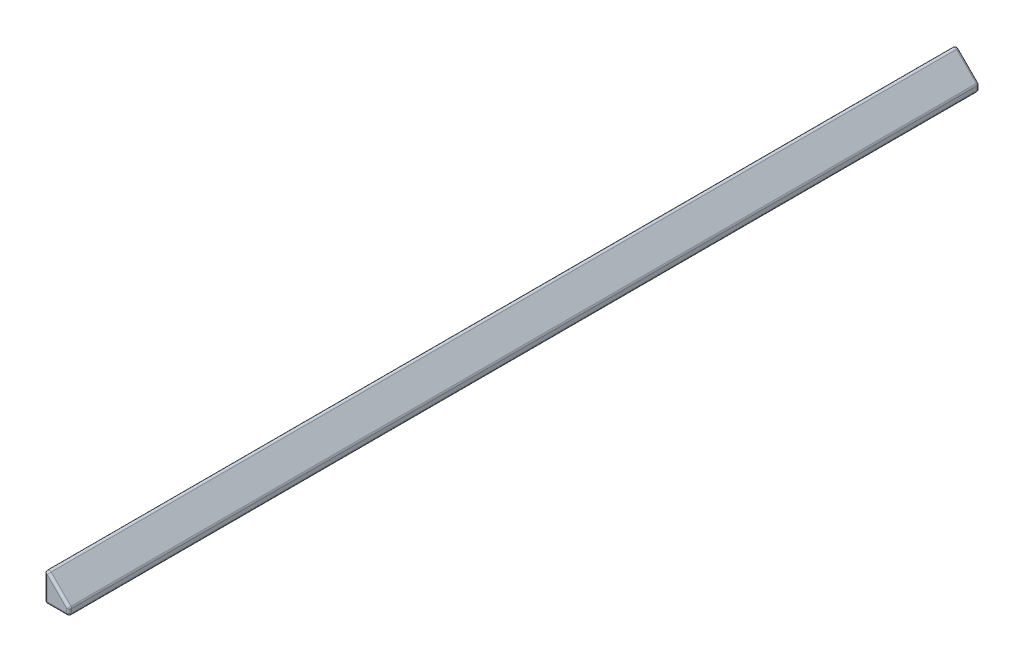
SolidWorks part; units mm, degrees
material "6061-T6 (SS)"
ref_plane "Front Plane" through (0, 0, 0) normal (0, 0, 1) x (1, 0, 0)
ref_plane "Top Plane" through (0, 0, 0) normal (0, 1, 0) x (1, 0, 0)
ref_plane "Right Plane" through (0, 0, 0) normal (1, 0, 0) x (0, 0, -1)
sketch "Sketch1" plane through (0, 0, 0) normal (0, 0, 1) x (1, 0, 0)
  line L5 (0, 0) -> (2.6, 0)
  line L6 (2.6, 0) -> (0, 2.6)
  line L7 (0, 2.6) -> (0, 0)
  line L11 (2, 0) -> (2, 0.6)
  point P2 (0, 0)
  point P4 (222.6177, 0)
  point P6 (0, 0)
  point P7 (0, 0)
  dimension "D1" = 0.6
  dimension "D2" = 2.6
extrude "Boss-Extrude1" add sketch "Sketch1" against normal mid plane 73.8 contours L5 L11 L6 L7 region at (0.7917, 0.9042, 0)
fillet "Fillet1" radius 0.2 12 edges at (0, 2.6, 0) (0, 0, 0) (2, 0.6, 0) (2, 0, 0) (2, 0.3, -36.9) (1, 1.6, -36.9) (0, 1.3, -36.9) (1, 0, -36.9) (0, 1.3, 36.9) (1, 1.6, 36.9) (2, 0.3, 36.9) (1, 0, 36.9)
